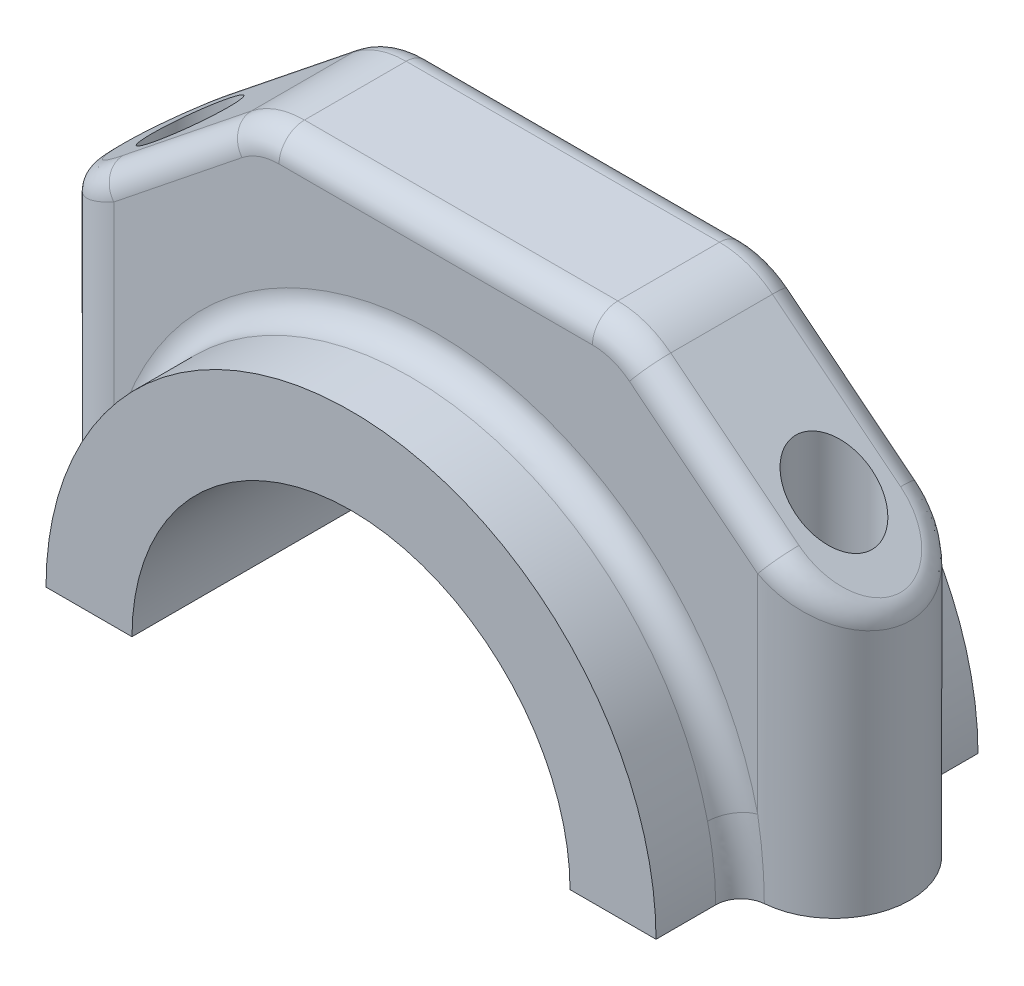
SolidWorks part; units mm, degrees
ref_plane "Front Plane" through (0, 0, 0) normal (0, 0, 1) x (1, 0, 0)
ref_plane "Top Plane" through (0, 0, 0) normal (0, 1, 0) x (1, 0, 0)
ref_plane "Right Plane" through (0, 0, 0) normal (1, 0, 0) x (0, 0, -1)
sketch "Sketch1" plane through (0, 0, 0) normal (0, 0, 1) x (1, 0, 0)
  line L0 (-36, 0) -> (-25.8515, 0)
  line L1 (25.8515, 0) -> (36, 0)
  arc A0 (36, 0) -> (-36, 0) centre (0, 0) ccw
  arc A1 (25.8515, 0) -> (-25.8515, 0) centre (0, 0) ccw
  dimension "D1" = 72
  dimension "D2" = 51.7031
extrude "Boss-Extrude1" add sketch "Sketch1" along normal mid plane 38
ref_plane "Plane1" through (0, 50, 0) normal (0, -1, 0) x (-1, 0, 0)
sketch "Sketch2" plane through (0, 50, 0) normal (0, -1, 0) x (-1, 0, 0)
  line L0 (-38, 0) -> (38, 0) construction
  line L1 (-38, 9) -> (38, 9)
  line L2 (-38, -9) -> (38, -9)
  arc A0 (-38, 9) -> (-38, -9) centre (-38, 0) ccw
  arc A1 (38, -9) -> (38, 9) centre (38, 0) ccw
  point P2 (0, 0)
  dimension "D2" = 9
  dimension "D1" = 76
extrude "Boss-Extrude2" add sketch "Sketch2" along normal up to surface (50 mm away) up to face at (-30.9258, 0, 0)
sketch "Sketch3" plane through (0, 0, 9) normal (0, 0, 1) x (1, 0, 0)
  line L1 (-25.8515, 0) -> (25.8515, 0)
  line L2 (-25.8515, 0) -> (25.8515, 0)
  arc A1 (25.8515, 0) -> (-25.8515, 0) centre (0, 0) ccw
  arc A2 (25.8515, 0) -> (-25.8515, 0) centre (0, 0) ccw
  dimension "D1" = 0
extrude "Cut-Extrude1" cut sketch "Sketch3" against normal through all
sketch "Sketch5" plane through (0, 0, 0) normal (0, -1, 0) x (1, 0, 0)
  circle A0 centre (-38, 0) radius 4.5
  circle A1 centre (38, 0) radius 4.5
  dimension "D1" = 9
  dimension "D2" = 9
extrude "Cut-Extrude2" cut sketch "Sketch5" against normal through all
sketch "Sketch7" plane through (0, 0, 0) normal (0, 0, 1) x (1, 0, 0)
  line L0 (-47, 50) -> (-47, 30)
  line L1 (-47, 50) -> (-47, 0) construction
  line L2 (-47, 30) -> (-22, 50)
  line L3 (38, 50) -> (-38, 50) construction
  line L4 (-22, 50) -> (-47, 50)
  line L5 (0, 0) -> (0, 20.1898) construction
  line L6 (22, 50) -> (47, 50)
  line L7 (47, 30) -> (22, 50)
  line L8 (47, 50) -> (47, 30)
  dimension "D1" = 20
  dimension "D2" = 25
extrude "Cut-Extrude3" cut sketch "Sketch7" against normal through all both and the other way through all
fillet "Fillet1" radius 10 2 edges at (-22, 50, 0) (22, 50, 0)
fillet "Fillet2" radius 3 14 edges at (-21.8023, 49.4363, -9) (-31.3696, 42.5043, -9) (-47, 30, 0) (-31.3696, 42.5043, 9) (-21.8023, 49.4363, 9) (0, 50, 9) (21.8023, 49.4363, 9) (31.3696, 42.5043, 9) (47, 30, 0) (31.3696, 42.5043, -9) (21.8023, 49.4363, -9) (0, 36, 9) (0, 50, -9) (0, 36, -9)
